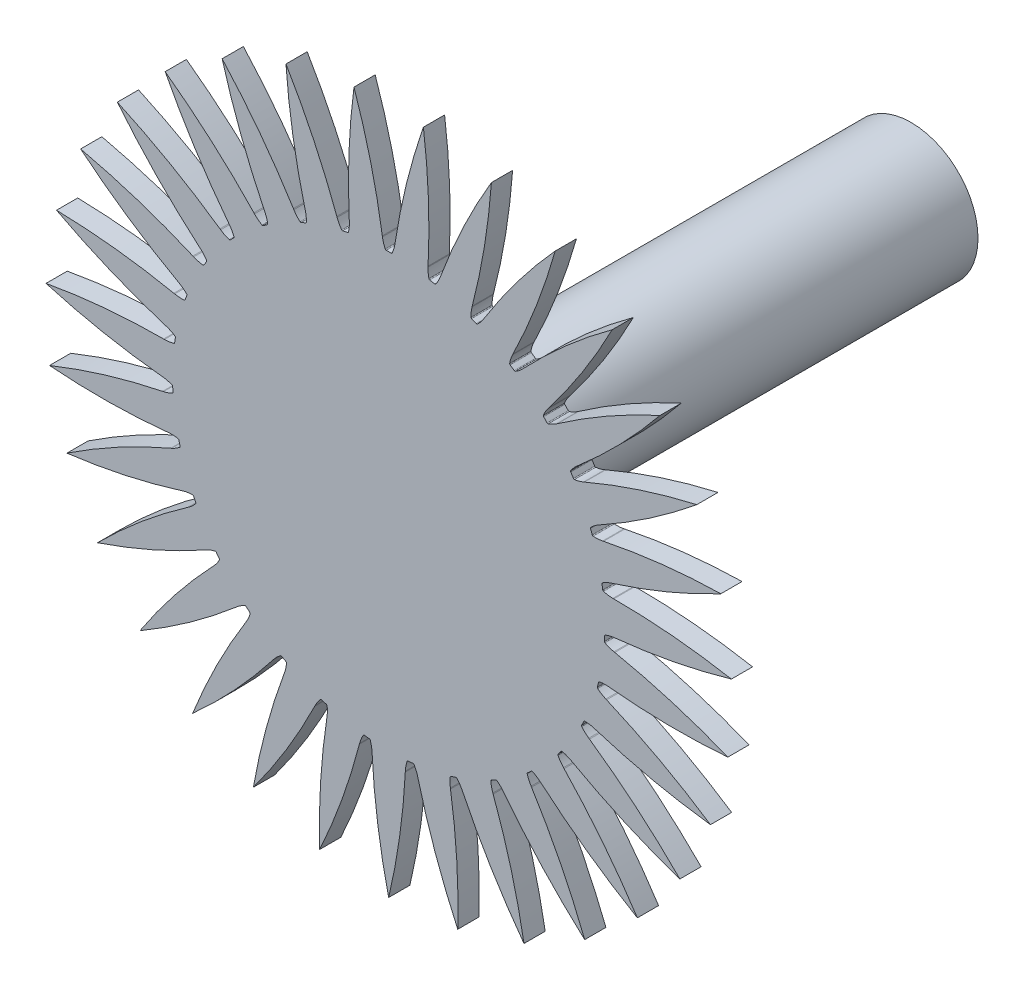
SolidWorks part; units mm, degrees
material "Pure Gold"
ref_plane "Front" through (0, 0, 0) normal (0, 0, 1) x (1, 0, 0)
ref_plane "Top" through (0, 0, 0) normal (0, 1, 0) x (1, 0, 0)
ref_plane "Right" through (0, 0, 0) normal (1, 0, 0) x (0, 0, -1)
sketch "Sketch1" plane through (0, 0, 0) normal (0, 0, 1) x (1, 0, 0)
  line L0 (0, 0) -> (0, 500) construction
  circle A1 centre (0, 0) radius 500
  dimension "D1" = 1000
extrude "Extrude1" add sketch "Sketch1" along normal blind 12.7
sketch "Sketch2" plane through (0, 0, 12.7) normal (0, 0, 1) x (1, 0, 0)
  line L0 (0, 0) -> (0, 500) construction
  line L1 (3.7322, 135.1942) -> (3.81, 135.7022)
  line L2 (-3.7322, 135.1942) -> (-3.81, 135.7022)
  circle A0 centre (0, 0) radius 500 construction
  arc A1 (1.905, 129.3522) -> (-1.905, 129.3522) centre (0, 0) ccw
  arc A2 (1.905, 129.3522) -> (3.7322, 135.1942) centre (-16.3537, 138.2697) ccw
  arc A3 (3.81, 135.7022) -> (241.2315, 437.9582) centre (390.2485, 76.5306) cw
  arc A4 (-3.81, 135.7022) -> (-241.2315, 437.9582) centre (-390.2485, 76.5306) ccw
  arc A5 (-1.905, 129.3522) -> (-3.7322, 135.1942) centre (16.3537, 138.2697) cw
  dimension "D1" = 7.62
  dimension "D2" = 20.32
  dimension "D4" = 6.35
  dimension "D5" = 3.81
  dimension "D6" = 129.3662
  dimension "D7" = 390.9425
  dimension "D3" = 0.508
extrude "Cut-Extrude1" cut sketch "Sketch2" against normal through all and the other way through all flip side to cut
fillet "Fillet1" radius 0.635 2 edges at (1.905, 129.3522, 6.35) (-1.905, 129.3522, 6.35)
pattern_circular "CirPattern1" count 31 over 360 about axis through (0, 0, 12.7) along (0, 0, -1) of "Cut-Extrude1", "Fillet1"
sketch "Sketch3" plane through (0, 0, 0) normal (0, 0, -1) x (-1, 0, 0)
  circle A0 centre (0, 0) radius 40
  dimension "D1" = 80
extrude "Extrude2" add sketch "Sketch3" along normal blind 300
equation "\"wheelSize\"= 100cm"
equation "\"D1@Sketch1\"=\"wheelSize\""
equation "\"D1@Sketch3\" = \"HoleMountDiameter@PrintingPress.Assembly\""
equation "\"D1@Extrude2\" = 3 * \"RivetLength@PrintingPress.Assembly\""
